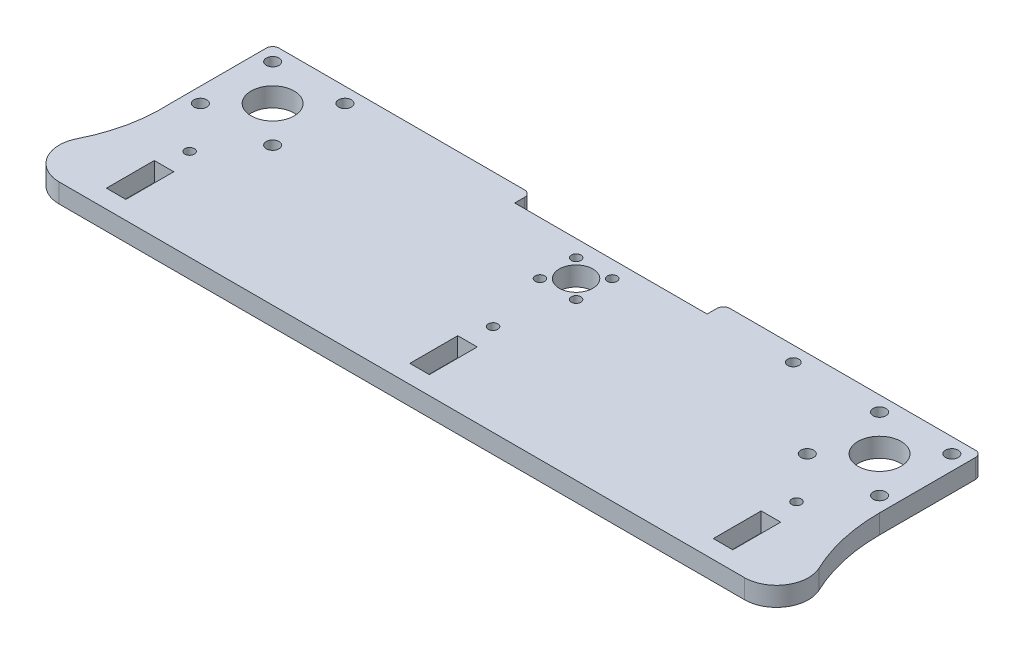
SolidWorks part; units mm, degrees
ref_plane "Alzado" through (0, 0, 0) normal (0, 0, 1) x (1, 0, 0)
ref_plane "Planta" through (0, 0, 0) normal (0, 1, 0) x (1, 0, 0)
ref_plane "Vista lateral" through (0, 0, 0) normal (1, 0, 0) x (0, 0, -1)
sketch "Croquis1" plane through (0, 0, 0) normal (0, 1, 0) x (1, 0, 0)
  line L0 (16.2827, 43.6446) -> (71.803, 43.6446)
  line L1 (-124.8326, 43.6446) -> (-103.4683, 43.6446)
  line L2 (-126.8326, 41.6446) -> (-126.8326, 11.6447)
  line L3 (-103.4683, 43.6446) -> (-60.497, 43.6446)
  line L4 (14.2827, 41.6446) -> (14.2827, 38.5546)
  line L5 (14.2827, 38.5546) -> (-45.948, 38.5546)
  line L6 (-126.8326, 27.6446) -> (-126.8326, 11.6446)
  line L7 (-126.8326, 11.6446) -> (-126.8326, 43.6446)
  line L8 (-60.497, 43.6446) -> (-47.948, 43.6446)
  line L9 (95.1674, 41.6446) -> (95.1674, 11.6447)
  line L10 (93.1674, 43.6446) -> (71.803, 43.6446)
  line L11 (-45.948, 41.6446) -> (-45.948, 38.5546)
  line L12 (-24.1326, 19.3446) -> (-7.5326, 35.9446) construction
  line L13 (-122.9609, -27.0571) -> (91.6208, -27.0571)
  line L14 (-24.1326, 35.9446) -> (-7.5326, 19.3446) construction
  line L15 (-126.8326, 43.6446) -> (-94.8326, 11.6446) construction
  line L16 (-126.8326, 11.6446) -> (-94.8326, 43.6446) construction
  line L17 (-126.8326, 11.6446) -> (-94.8326, 11.6446) construction
  line L18 (-94.8326, 11.6446) -> (95.1674, 11.6447) construction
  line L19 (67.8536, 38.9583) -> (29.9814, 38.9583) construction
  line L22 (-113.8826, -6.3554) -> (-107.7826, -6.3554)
  line L23 (-113.8826, -6.3554) -> (-113.8826, -21.3554)
  line L24 (-113.8826, -21.3554) -> (-107.7826, -21.3554)
  line L25 (-107.7826, -6.3554) -> (-107.7826, -21.3554)
  line L27 (76.1174, -6.3554) -> (76.1174, -21.3554)
  line L28 (82.2174, -21.3553) -> (76.1174, -21.3554)
  line L29 (82.2174, -6.3553) -> (82.2174, -21.3553)
  line L30 (82.2174, -6.3553) -> (76.1174, -6.3554)
  line L31 (-18.8826, -6.3554) -> (-18.8826, -21.3554)
  line L32 (-12.7826, -21.3553) -> (-18.8826, -21.3554)
  line L33 (-12.7826, -6.3553) -> (-12.7826, -21.3553)
  line L34 (-12.7826, -6.3553) -> (-18.8826, -6.3554)
  line L35 (79.1674, 1.6446) -> (-110.8326, 1.6446) construction
  circle A0 centre (-15.8326, 27.6446) radius 5.25
  circle A1 centre (-110.8326, 27.6446) radius 6.75
  circle A2 centre (79.1674, 27.6446) radius 6.75
  arc A3 (91.6208, -27.0571) -> (100.6583, -12.7766) centre (91.6208, -17.0571) ccw
  circle A4 centre (-99.5189, 38.9583) radius 2
  circle A5 centre (-122.1464, 38.9583) radius 2
  circle A6 centre (-99.5189, 16.3309) radius 2
  circle A7 centre (-122.1464, 16.3309) radius 2
  circle A8 centre (90.4811, 16.3309) radius 2
  circle A9 centre (67.8536, 16.3309) radius 2
  circle A10 centre (67.8536, 38.9583) radius 2
  arc A11 (-126.8326, 11.6447) -> (-131.8924, -12.5595) centre (-174.7801, 9.0369) cw
  arc A12 (95.1674, 11.6447) -> (100.6583, -12.7766) centre (152.2197, 11.6447) ccw
  arc A13 (-131.8924, -12.5595) -> (-122.9609, -27.0571) centre (-122.9609, -17.0571) ccw
  circle A14 centre (-10.1758, 33.3015) radius 1.5
  circle A15 centre (-21.4895, 33.3015) radius 1.5
  circle A16 centre (-21.4895, 21.9878) radius 1.5
  circle A17 centre (-10.1758, 21.9878) radius 1.5
  circle A18 centre (-110.8326, 1.6446) radius 1.5
  circle A19 centre (40.8536, 38.9583) radius 1.75
  arc A20 (93.1674, 43.6446) -> (95.1674, 41.6446) centre (93.1674, 41.6446) cw
  arc A21 (-126.8326, 41.6446) -> (-124.8326, 43.6446) centre (-124.8326, 41.6446) cw
  circle A23 centre (79.1674, 1.6446) radius 1.5
  arc A24 (-47.948, 43.6446) -> (-45.948, 41.6446) centre (-47.948, 41.6446) cw
  circle A25 centre (90.4811, 38.9583) radius 2
  arc A26 (14.2827, 41.6446) -> (16.2827, 43.6446) centre (16.2827, 41.6446) cw
  circle A28 centre (-15.828, 1.6446) radius 1.5
  point P51 (-15.8326, 43.6446)
  dimension "D1" = 10.5
  dimension "D2" = 13.5
  dimension "D4" = 13.5
  dimension "D5" = 4
  dimension "D6" = 4
  dimension "D7" = 4
  dimension "D8" = 4
  dimension "D9" = 2
  dimension "D21" = 10
  dimension "D25" = 27
  dimension "D3" = 95
  dimension "D10" = 5.2532
  dimension "D11" = 5.2532
  dimension "D12" = 11.3137
  dimension "D13" = 11.3137
  dimension "D14" = 11.3137
  dimension "D15" = 11.3137
  dimension "D16" = 10
  dimension "D17" = 16
  dimension "D18" = 6.1
  dimension "D19" = 15
  dimension "D20" = 8
  dimension "D22" = 10
  dimension "D23" = 10
  dimension "D24" = 22.6274
extrude "Saliente-Extruir1" add sketch "Croquis1" along normal blind 6 contours A26 L4 L5 L11 A24 L8 L3 L1 A21 L2 L6 A11 A13 L13 A3 A12 L9 A20 L10 L0 A25 A10 A8 A7 A6 A5 A4 A2 A1 A0 L34 L33 L32 L31 L30 L29 L28 L27 region at (-15.7703, 0, -7.0246)
